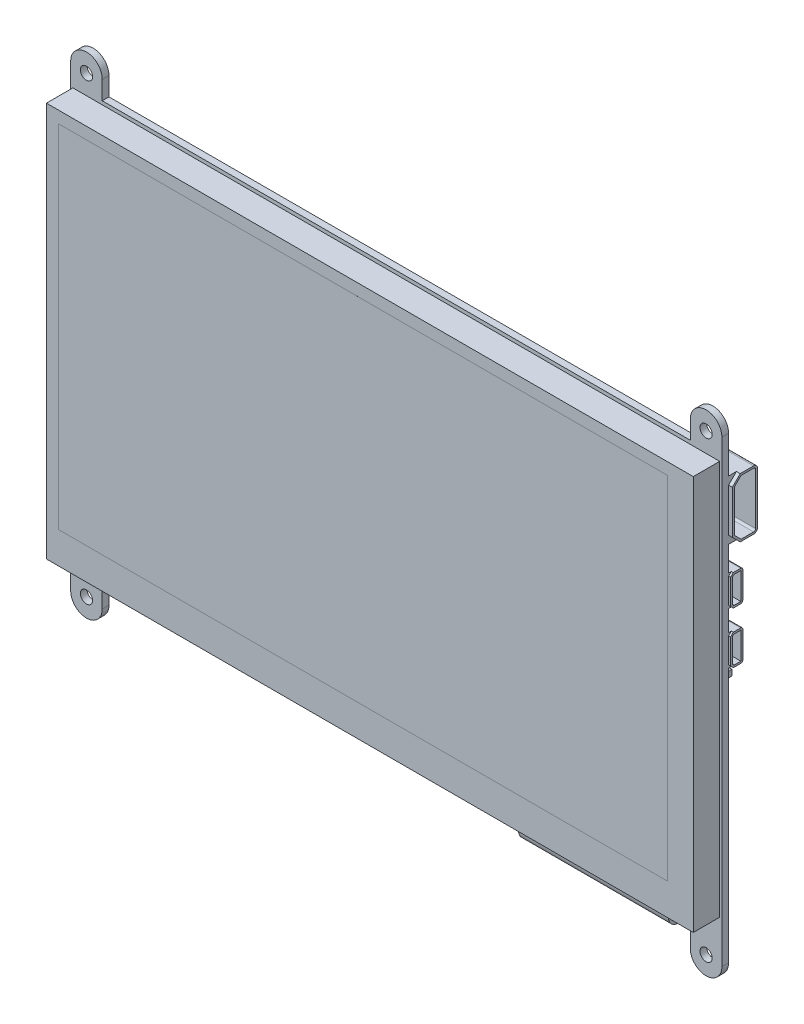
SolidWorks part; units mm, degrees
ref_plane "Přední rovina" through (0, 0, 0) normal (0, 0, 1) x (1, 0, 0)
ref_plane "Horní rovina" through (0, 0, 0) normal (0, 1, 0) x (1, 0, 0)
ref_plane "Pravá rovina" through (0, 0, 0) normal (1, 0, 0) x (0, 0, -1)
sketch "Skica1" plane through (0, 0, 0) normal (0, 0, 1) x (1, 0, 0)
  line L1 (-82, -50.05) -> (82, -50.05)
  line L2 (-82, -50.05) -> (-82, 50.05)
  line L3 (-82, 50.05) -> (82, 50.05)
  line L4 (82, -50.05) -> (82, 50.05)
  line L5 (-82, -50.05) -> (82, 50.05) construction
  line L6 (-82, 50.05) -> (82, -50.05) construction
  line L7 (-82.55, -55.95) -> (82.55, -55.95)
  line L8 (-82.55, -55.95) -> (-82.55, 50.95)
  line L9 (-82.55, 50.95) -> (82.55, 50.95)
  line L10 (82.55, -55.95) -> (82.55, 50.95)
  line L11 (-82.55, -55.95) -> (82.55, 50.95) construction
  line L12 (-82.55, 50.95) -> (82.55, -55.95) construction
  point P0 (0, 0)
  point P6 (0, -2.5)
  dimension "D1" = 100.1
  dimension "D2" = 164
  dimension "D3" = 106.9
  dimension "D4" = 0.55
  dimension "D5" = 0.55
  dimension "D6" = 0.9
extrude "Přidat vysunutím1" add sketch "Skica1" along normal blind 6.7 contours L1 L4 L3 L2 region at (0, 0, 0)
extrude "Přidat vysunutím2" add sketch "Skica1<3>" against normal blind 1.7 contours L10 L9 L8 L7
sketch "Skica1<3>" plane through (0, 0, 0) normal (0, 0, 1) x (1, 0, 0) same geometry as "Skica1"
sketch "Skica2" plane through (0, 0, -1.7) normal (0, 0, -1) x (-1, 0, 0)
  line L0 (0, 0) -> (0, -91.8363) construction
  line L1 (-82.55, -2.5) -> (0, -2.5) construction
  line L2 (-82.55, -55.95) -> (-82.55, 50.95) construction
  line L3 (-78.55, 50.95) -> (-78.55, 55.65) construction
  line L4 (82.55, 50.95) -> (-82.55, 50.95) construction
  line L5 (-82.55, 50.95) -> (-82.55, 55.65)
  line L6 (-74.55, 50.95) -> (-74.55, 55.65)
  line L7 (-78.55, -55.95) -> (-78.55, -60.65) construction
  line L8 (-82.55, -55.95) -> (-82.55, -60.65)
  line L9 (-74.55, -55.95) -> (-74.55, -60.65)
  line L10 (-78.55, -55.95) -> (-78.55, -60.65) construction
  line L11 (-82.55, -55.95) -> (-82.55, -60.65)
  line L12 (-74.55, -55.95) -> (-74.55, -60.65)
  line L13 (-78.55, 50.95) -> (-78.55, 55.65) construction
  line L14 (-82.55, 50.95) -> (-82.55, 55.65)
  line L15 (-74.55, 50.95) -> (-74.55, 55.65)
  line L16 (78.55, 50.95) -> (78.55, 55.65) construction
  line L17 (82.55, 50.95) -> (82.55, 55.65)
  line L18 (74.55, 50.95) -> (74.55, 55.65)
  line L19 (78.55, -55.95) -> (78.55, -60.65) construction
  line L20 (82.55, -55.95) -> (82.55, -60.65)
  line L21 (74.55, -55.95) -> (74.55, -60.65)
  line L22 (78.55, -55.95) -> (78.55, -60.65) construction
  line L23 (82.55, -55.95) -> (82.55, -60.65)
  line L24 (74.55, -55.95) -> (74.55, -60.65)
  line L25 (78.55, 50.95) -> (78.55, 55.65) construction
  line L26 (82.55, 50.95) -> (82.55, 55.65)
  line L27 (74.55, 50.95) -> (74.55, 55.65)
  arc A0 (-82.55, 50.95) -> (-74.55, 50.95) centre (-78.55, 50.95) ccw
  arc A1 (-74.55, 55.65) -> (-82.55, 55.65) centre (-78.55, 55.65) ccw
  circle A2 centre (-78.55, 55) radius 1.55
  circle A3 centre (-78.55, -60) radius 1.55
  arc A4 (-82.55, -55.95) -> (-74.55, -55.95) centre (-78.55, -55.95) cw
  arc A5 (-74.55, -60.65) -> (-82.55, -60.65) centre (-78.55, -60.65) cw
  arc A6 (-82.55, -55.95) -> (-74.55, -55.95) centre (-78.55, -55.95) cw
  arc A7 (-74.55, -60.65) -> (-82.55, -60.65) centre (-78.55, -60.65) cw
  arc A8 (-82.55, 50.95) -> (-74.55, 50.95) centre (-78.55, 50.95) ccw
  arc A9 (-74.55, 55.65) -> (-82.55, 55.65) centre (-78.55, 55.65) ccw
  circle A10 centre (-78.55, 55) radius 1.55
  circle A11 centre (-78.55, -60) radius 1.55
  circle A12 centre (78.55, -60) radius 1.55
  circle A13 centre (78.55, 55) radius 1.55
  circle A14 centre (78.55, -60) radius 1.55
  circle A15 centre (78.55, 55) radius 1.55
  arc A16 (82.55, 50.95) -> (74.55, 50.95) centre (78.55, 50.95) cw
  arc A17 (74.55, 55.65) -> (82.55, 55.65) centre (78.55, 55.65) cw
  arc A18 (82.55, -55.95) -> (74.55, -55.95) centre (78.55, -55.95) ccw
  arc A19 (74.55, -60.65) -> (82.55, -60.65) centre (78.55, -60.65) ccw
  arc A20 (82.55, -55.95) -> (74.55, -55.95) centre (78.55, -55.95) ccw
  arc A21 (74.55, -60.65) -> (82.55, -60.65) centre (78.55, -60.65) ccw
  arc A22 (82.55, 50.95) -> (74.55, 50.95) centre (78.55, 50.95) cw
  arc A23 (74.55, 55.65) -> (82.55, 55.65) centre (78.55, 55.65) cw
  point P11 (-78.55, 53.3)
  point P18 (-78.55, 59.65)
  point P23 (-78.55, -58.3)
  point P30 (-78.55, -58.3)
  point P37 (-78.55, 53.3)
  point P52 (78.55, 53.3)
  point P59 (78.55, -58.3)
  point P66 (78.55, -58.3)
  point P73 (78.55, 53.3)
  line M7 (-82.55, -55.95) -> (82.55, -55.95)
  line M9 (82.55, 50.95) -> (-82.55, 50.95)
  dimension "D1" = 8.7
  dimension "D2" = 3.1
  dimension "D4" = 3.1
  dimension "D3" = 8
extrude "Přidat vysunutím3" add sketch "Skica2" against normal up to surface (1.7 mm away) contours A5 L9 L8 A3 M7 | L21 A19 L20 A12 M7 | A17 L18 L17 A13 M9 | L6 A1 L5 A2 M9 region at (-74.6682, 53.3, -1.7) region at (82.4318, 53.3, -1.7) region at (78.55, -56.0682, -1.7) region at (-78.55, -56.0682, -1.7) up to face at (0, -2.5, 0)
sketch "Skica3" plane through (0, 0, 6.7) normal (0, 0, 1) x (1, 0, 0)
  line L0 (-82, 50.05) -> (82, 50.05) construction
  line L1 (75.5, 47.05) -> (-79, 47.05)
  line L2 (75.5, 47.05) -> (75.5, -42.05)
  line L3 (75.5, -42.05) -> (-79, -42.05)
  line L4 (-79, 47.05) -> (-79, -42.05)
  line L5 (75.5, 47.05) -> (-79, -42.05) construction
  line L6 (75.5, -42.05) -> (-79, 47.05) construction
  line L7 (-82, -50.05) -> (82, -50.05) construction
  line L8 (-82, -50.05) -> (-82, 50.05) construction
  line L9 (82, -50.05) -> (82, 50.05) construction
  point P0 (-1.75, 2.5)
  dimension "D1" = 3
  dimension "D2" = 8
  dimension "D3" = 3
  dimension "D4" = 6.5
extrude "Odebrat vysunutím1" cut sketch "Skica3" against normal blind 1.5
extrude "Přidat vysunutím4" add sketch "Skica3<2>" against normal blind 1.5 separate body
sketch "Skica3<2>" plane through (0, 0, 6.7) normal (0, 0, 1) x (1, 0, 0) same geometry as "Skica3"
sketch "Skica4" plane through (0, 0, 0) normal (0, 0, 1) x (1, 0, 0)
  line L0 (-82, -50.05) -> (82, -50.05) construction
  line L1 (75.3, -50.05) -> (37.3, -50.05)
  line L2 (75.3, -50.05) -> (75.3, -52.8)
  line L3 (75.3, -52.8) -> (37.3, -52.8)
  line L4 (37.3, -50.05) -> (37.3, -52.8)
  dimension "D1" = 38
  dimension "D2" = 2.75
  dimension "D3" = 6.7
extrude "Přidat vysunutím5" add sketch "Skica4" along normal blind 6.3
fillet "Zaoblit1" radius 2.5 1 edges at (56.3, -52.8, 6.3)
sketch "Skica5" plane through (0, 0, 0) normal (0, 0, 1) x (1, 0, 0)
  line L0 (-82, -50.05) -> (37.3, -50.05) construction
  line L1 (-14.55, -50.05) -> (13.95, -50.05)
  line L2 (-14.55, -50.05) -> (-14.55, -50.95)
  line L3 (-14.55, -50.95) -> (13.95, -50.95)
  line L4 (13.95, -50.05) -> (13.95, -50.95)
  line L5 (82.55, -60.65) -> (82.55, 55.65) construction
  dimension "D1" = 28.5
  dimension "D2" = 0.9
  dimension "D3" = 68.6
extrude "Přidat vysunutím6" add sketch "Skica5" along normal blind 4.3
fillet "Zaoblit2" radius 3 1 edges at (-0.3, -50.95, 4.3)
sketch "Skica6" plane through (0, 0, -1.7) normal (0, 0, -1) x (-1, 0, 0)
  line L0 (74.55, 50.95) -> (-74.55, 50.95) construction
  line L1 (-21.65, 11.45) -> (-1.75, 11.45)
  line L2 (-21.65, 11.45) -> (-21.65, 25.25)
  line L3 (-21.65, 25.25) -> (-1.75, 25.25)
  line L4 (-1.75, 11.45) -> (-1.75, 25.25)
  line L5 (-21.65, 11.45) -> (-1.75, 25.25) construction
  line L6 (-21.65, 25.25) -> (-1.75, 11.45) construction
  line L7 (-23.55, 11.95) -> (0.15, 11.95)
  line L8 (-23.55, 11.95) -> (-23.55, 24.75)
  line L9 (-23.55, 24.75) -> (0.15, 24.75)
  line L10 (0.15, 11.95) -> (0.15, 24.75)
  line L11 (-23.55, 11.95) -> (0.15, 24.75) construction
  line L12 (-23.55, 24.75) -> (0.15, 11.95) construction
  line L13 (-21.1, 9.45) -> (-2.3, 9.45)
  line L14 (-21.1, 9.45) -> (-21.1, 27.25)
  line L15 (-21.1, 27.25) -> (-2.3, 27.25)
  line L16 (-2.3, 9.45) -> (-2.3, 27.25)
  line L17 (-21.1, 9.45) -> (-2.3, 27.25) construction
  line L18 (-21.1, 27.25) -> (-2.3, 9.45) construction
  line L19 (-82.55, -60.65) -> (-82.55, 55.65) construction
  line L20 (82.55, -60.65) -> (82.55, 55.65) construction
  line L21 (32.45, 6.95) -> (66.45, 6.95)
  line L22 (32.45, 6.95) -> (32.45, 29.35)
  line L23 (32.45, 29.35) -> (66.45, 29.35)
  line L24 (66.45, 6.95) -> (66.45, 29.35)
  line L25 (26.55, 23.25) -> (18.25, 23.25)
  line L26 (26.55, 23.25) -> (26.55, 6.85)
  line L27 (26.55, 6.85) -> (18.25, 6.85)
  line L28 (18.25, 23.25) -> (18.25, 6.85)
  line L29 (18.25, 23.25) -> (13.85, 23.25)
  line L30 (18.25, 23.25) -> (18.25, 12.25)
  line L31 (18.25, 12.25) -> (13.85, 12.25)
  line L32 (13.85, 23.25) -> (13.85, 12.25)
  line L33 (2.75, 12.85) -> (5.65, 12.85)
  line L34 (2.75, 12.85) -> (2.75, 30.05)
  line L35 (2.75, 30.05) -> (5.65, 30.05)
  line L36 (5.65, 12.85) -> (5.65, 30.05)
  line L37 (5.65, 30.05) -> (9.75, 30.05)
  line L38 (5.65, 30.05) -> (5.65, 25.75)
  line L39 (5.65, 25.75) -> (9.75, 25.75)
  line L40 (9.75, 30.05) -> (9.75, 25.75)
  point P0 (-11.7, 18.35)
  point P5 (-11.7, 18.35)
  point P10 (-11.7, 18.35)
  point P40 (9.75, 27.9)
  dimension "D1" = 19.9
  dimension "D2" = 13.8
  dimension "D3" = 12.8
  dimension "D4" = 18.8
  dimension "D5" = 23.7
  dimension "D6" = 17.8
  dimension "D7" = 25.7
  dimension "D8" = 60.9
  dimension "D9" = 34
  dimension "D10" = 22.4
  dimension "D11" = 16.1
  dimension "D12" = 21.6
  dimension "D13" = 8.3
  dimension "D14" = 12.7
  dimension "D15" = 16.4
  dimension "D16" = 11
  dimension "D17" = 27.7
  dimension "D18" = 56
  dimension "D19" = 17.2
  dimension "D20" = 7
  dimension "D21" = 4.3
  dimension "D22" = 20.9
  dimension "D23" = 72.8
  dimension "D24" = 2.9
extrude "Přidat vysunutím7" add sketch "Skica6" along normal blind 2.4 contours L21 L24 L23 L22 region at (-49.45, 18.15, -1.7)
extrude "Přidat vysunutím8" add sketch "Skica6<3>" along normal blind 1.8 contours L25 L28 L27 L26 region at (-22.4, 15.05, -1.7)
sketch "Skica6<3>" plane through (0, 0, -1.7) normal (0, 0, -1) x (-1, 0, 0) same geometry as "Skica6"
extrude "Přidat vysunutím9" add sketch "Skica6<4>" along normal blind 1 contours L29 L32 L31 L28 region at (-16.05, 17.75, -1.7)
sketch "Skica6<4>" plane through (0, 0, -1.7) normal (0, 0, -1) x (-1, 0, 0) same geometry as "Skica6"
extrude "Přidat vysunutím10" add sketch "Skica6<5>" along normal blind 1 contours L33 L36 L35 L34 | L37 L40 L39 L38 region at (-4.2, 21.45, -1.7)
sketch "Skica6<5>" plane through (0, 0, -1.7) normal (0, 0, -1) x (-1, 0, 0) same geometry as "Skica6"
extrude "Přidat vysunutím11" add sketch "Skica6<6>" along normal blind 1.45 contours L2 L3 L4 L1
sketch "Skica6<6>" plane through (0, 0, -1.7) normal (0, 0, -1) x (-1, 0, 0) same geometry as "Skica6"
extrude "Přidat vysunutím12" add sketch "Skica6<7>" along normal blind 0.8 contours L7 L10 L9 L4 | L15 L16 L13 L14 | L8 L9 L10 L7 region at (0.8, 18.35, -1.7)
sketch "Skica6<7>" plane through (0, 0, -1.7) normal (0, 0, -1) x (-1, 0, 0) same geometry as "Skica6"
chamfer "Zkosení1" distance 0.8 angle 45 4 edges at (11.7, 27.25, -2.5) (23.55, 18.35, -2.5) (-0.15, 18.35, -2.5) (11.7, 9.45, -2.5)
sketch "Skica7" plane through (0, 0, -1.7) normal (0, 0, -1) x (-1, 0, 0)
  line L0 (74.55, -55.95) -> (-74.55, -55.95) construction
  line L1 (-35.45, -32.65) -> (-28.65, -32.65)
  line L2 (-35.45, -32.65) -> (-35.45, -25.85)
  line L3 (-35.45, -25.85) -> (-28.65, -25.85)
  line L4 (-28.65, -32.65) -> (-28.65, -25.85)
  line L5 (-35.45, -32.65) -> (-28.65, -25.85) construction
  line L6 (-35.45, -25.85) -> (-28.65, -32.65) construction
  line L7 (-34.9, -34.25) -> (-29.2, -34.25)
  line L8 (-34.9, -34.25) -> (-34.9, -24.25)
  line L9 (-34.9, -24.25) -> (-29.2, -24.25)
  line L10 (-29.2, -34.25) -> (-29.2, -24.25)
  line L11 (-34.9, -34.25) -> (-29.2, -24.25) construction
  line L12 (-34.9, -24.25) -> (-29.2, -34.25) construction
  line L13 (-37.05, -32.1) -> (-27.05, -32.1)
  line L14 (-37.05, -32.1) -> (-37.05, -26.4)
  line L15 (-37.05, -26.4) -> (-27.05, -26.4)
  line L16 (-27.05, -32.1) -> (-27.05, -26.4)
  line L17 (-37.05, -32.1) -> (-27.05, -26.4) construction
  line L18 (-37.05, -26.4) -> (-27.05, -32.1) construction
  line L19 (-82.55, -60.65) -> (-82.55, 55.65) construction
  line L20 (-45.9, -24.6) -> (-45.9, -31) construction
  line L21 (-24.15, -32.45) -> (-21.85, -32.45)
  line L22 (-24.15, -32.45) -> (-24.15, -24.65)
  line L23 (-24.15, -24.65) -> (-21.85, -24.65)
  line L24 (-21.85, -32.45) -> (-21.85, -24.65)
  line L25 (-34.05, -21.85) -> (-29.55, -21.85)
  line L26 (-34.05, -21.85) -> (-34.05, -19.35)
  line L27 (-34.05, -19.35) -> (-29.55, -19.35)
  line L28 (-29.55, -21.85) -> (-29.55, -19.35)
  line L29 (-42.15, -35.15) -> (-40.5, -35.15)
  line L30 (-42.15, -35.15) -> (-42.15, -24.85)
  line L31 (-42.15, -24.85) -> (-40.5, -24.85)
  line L32 (-40.5, -35.15) -> (-40.5, -24.85)
  line L33 (-40.5, -35.15) -> (-38.85, -35.15)
  line L34 (-40.5, -35.15) -> (-40.5, -29.25)
  line L35 (-40.5, -29.25) -> (-38.85, -29.25)
  line L36 (-38.85, -35.15) -> (-38.85, -29.25)
  line L37 (-44.15, -24.6) -> (-44.15, -31)
  line L38 (-47.65, -24.6) -> (-47.65, -31)
  line L39 (-45.9, -31) -> (-45.9, -24.6) construction
  line L40 (-48.15, -31) -> (-48.15, -24.6)
  line L41 (-43.65, -31) -> (-43.65, -24.6)
  line L43 (-29.55, -37.45) -> (-27.55, -37.45)
  line L44 (-29.55, -37.45) -> (-29.55, -36.15)
  line L45 (-29.55, -36.15) -> (-27.55, -36.15)
  line L46 (-27.55, -37.45) -> (-27.55, -36.15)
  arc A0 (-44.15, -24.6) -> (-47.65, -24.6) centre (-45.9, -24.6) ccw
  arc A1 (-47.65, -31) -> (-44.15, -31) centre (-45.9, -31) ccw
  arc A2 (-48.15, -31) -> (-43.65, -31) centre (-45.9, -31) ccw
  arc A3 (-43.65, -24.6) -> (-48.15, -24.6) centre (-45.9, -24.6) ccw
  point P0 (-32.05, -29.25)
  point P5 (-32.05, -29.25)
  point P10 (-32.05, -29.25)
  point P36 (-45.9, -27.8)
  point P41 (-45.9, -27.8)
  point P48 (-45.9, -32.75)
  point P49 (-47.65, -27.8)
  dimension "D10" = 23.2
  dimension "D1" = 6.8
  dimension "D2" = 5.7
  dimension "D3" = 10
  dimension "D4" = 23.3
  dimension "D5" = 47.1
  dimension "D6" = 4.5
  dimension "D7" = 3.5
  dimension "D8" = 9.9
  dimension "D9" = 34.9
  dimension "D11" = 3.3
  dimension "D12" = 10.3
  dimension "D13" = 5.9
  dimension "D14" = 20.8
  dimension "D15" = 40.4
  dimension "D16" = 2.3
  dimension "D17" = 7.8
  dimension "D18" = 23.5
  dimension "D19" = 4.5
  dimension "D20" = 4.5
  dimension "D21" = 2.5
  dimension "D22" = 4
  dimension "D23" = 48.5
  dimension "D24" = 2
  dimension "D25" = 1.3
  dimension "D26" = 18.5
  dimension "D27" = 53
extrude "Přidat vysunutím13" add sketch "Skica7" along normal blind 1.5 contours L1 L4 L3 L2
extrude "Přidat vysunutím14" add sketch "Skica7<3>" along normal blind 0.8 contours L16 L15 L14 L13 | L9 L10 L7 L8
sketch "Skica7<3>" plane through (0, 0, -1.7) normal (0, 0, -1) x (-1, 0, 0) same geometry as "Skica7"
extrude "Přidat vysunutím15" add sketch "Skica7<4>" along normal blind 0.7 contours L41 A3 L40 A2
sketch "Skica7<4>" plane through (0, 0, -1.7) normal (0, 0, -1) x (-1, 0, 0) same geometry as "Skica7"
extrude "Přidat vysunutím16" add sketch "Skica7<5>" along normal blind 4.2 contours L37 A1 L38 A0
sketch "Skica7<5>" plane through (0, 0, -1.7) normal (0, 0, -1) x (-1, 0, 0) same geometry as "Skica7"
extrude "Přidat vysunutím17" add sketch "Skica7<6>" along normal blind 0.8 contours L33 L36 L35 L34 | L29 L30 L31 L32 | L24 L23 L22 L21 | L43 L46 L45 L44 | L25 L28 L27 L26
sketch "Skica7<6>" plane through (0, 0, -1.7) normal (0, 0, -1) x (-1, 0, 0) same geometry as "Skica7"
chamfer "Zkosení2" distance 0.8 angle 45 4 edges at (32.05, -24.25, -2.5) (37.05, -29.25, -2.5) (27.05, -29.25, -2.5) (32.05, -34.25, -2.5)
sketch "Skica8" plane through (0, 0, -1.7) normal (0, 0, -1) x (-1, 0, 0)
  line L0 (74.55, -55.95) -> (-74.55, -55.95) construction
  line L1 (-17.15, -36.45) -> (20.55, -36.45)
  line L2 (-17.15, -36.45) -> (-17.15, -31.45)
  line L3 (-17.15, -31.45) -> (20.55, -31.45)
  line L4 (20.55, -36.45) -> (20.55, -31.45)
  line L5 (82.55, -60.65) -> (82.55, 55.65) construction
  dimension "D1" = 5
  dimension "D2" = 37.7
  dimension "D3" = 19.5
  dimension "D4" = 62
extrude "Odebrat vysunutím2" cut sketch "Skica8" against normal blind 1.6
sketch "Skica9" plane through (0, 0, -1.7) normal (0, 0, -1) x (-1, 0, 0)
  line L0 (1.1, -10.85) -> (1.1, -1.0919) construction
  line L1 (13.9, -12.85) -> (-11.7, -12.85)
  line L2 (13.9, -12.85) -> (13.9, -8.85)
  line L3 (13.9, -8.85) -> (-11.7, -8.85)
  line L4 (-11.7, -12.85) -> (-11.7, -8.85)
  line L5 (13.9, -12.85) -> (-11.7, -8.85) construction
  line L6 (13.9, -8.85) -> (-11.7, -12.85) construction
  line L7 (-14.05, -13.35) -> (-11.7, -13.35)
  line L8 (-14.05, -13.35) -> (-14.05, -8.35)
  line L9 (-14.05, -8.35) -> (-11.7, -8.35)
  line L10 (-11.7, -13.35) -> (-11.7, -8.35)
  line L11 (-14.05, -13.35) -> (-11.7, -8.35) construction
  line L12 (-14.05, -8.35) -> (-11.7, -13.35) construction
  line L13 (16.25, -8.35) -> (13.9, -13.35) construction
  line L14 (13.9, -12.85) -> (13.9, -8.85)
  line L15 (16.25, -13.35) -> (13.9, -8.35) construction
  line L16 (13.9, -13.35) -> (13.9, -8.35)
  line L17 (16.25, -13.35) -> (13.9, -13.35)
  line L18 (16.25, -8.35) -> (13.9, -8.35)
  line L19 (16.25, -13.35) -> (16.25, -8.35)
  line L20 (82.55, -60.65) -> (82.55, 55.65) construction
  line L21 (74.55, -55.95) -> (-74.55, -55.95) construction
  point P0 (1.1, -10.85)
  point P5 (-12.875, -10.85)
  point P10 (15.075, -10.85)
  dimension "D1" = 4
  dimension "D2" = 30.3
  dimension "D3" = 25.6
  dimension "D4" = 5
  dimension "D5" = 66.3
  dimension "D6" = 43.1
extrude "Přidat vysunutím18" add sketch "Skica9" along normal blind 2 contours L4 L1 L2 L3 region at (-1.1, -10.85, -1.7)
extrude "Přidat vysunutím19" add sketch "Skica9<3>" along normal blind 2.1 contours L8 L9 L10 L7 | L19 L18 L16 L17
sketch "Skica9<3>" plane through (0, 0, -1.7) normal (0, 0, -1) x (-1, 0, 0) same geometry as "Skica9"
chamfer "Zkosení3" distance 0.5 angle 45 1 edges at (-1.1, -8.85, -1.7)
sketch "Skica10" plane through (0, 0, -1.7) normal (0, 0, -1) x (-1, 0, 0)
  line L0 (13.9, -12.85) -> (-11.7, -12.85) construction
  line L1 (-11.7, -12.85) -> (13.9, -12.85)
  line L2 (-11.7, -12.85) -> (-11.7, -33.85)
  line L3 (-11.7, -33.85) -> (13.9, -33.85)
  line L4 (13.9, -12.85) -> (13.9, -33.85)
  line L5 (-14.6, -29.35) -> (-11.7, -24.85)
  line L6 (-11.7, -33.85) -> (-14.6, -33.85)
  line L7 (-11.7, -33.85) -> (-11.7, -29.35)
  line L8 (-11.7, -29.35) -> (-14.6, -29.35)
  line L9 (-14.6, -33.85) -> (-14.6, -29.35)
  dimension "D1" = 21
  dimension "D2" = 28.5
  dimension "D3" = 16.5
  dimension "D4" = 4.5
extrude "Přidat vysunutím20" add sketch "Skica10" along direction (0, 0, 1) on the side against the normal up to surface (1.6 mm away) and the other way blind 1.25 contours L4 L1 L2 L3 | L9 L6 L2 L8 | L8 L2 L5 region at (-1.1, -23.35, -1.7) region at (12.6667, -27.85, -1.7) region at (13.15, -31.6, -1.7) up to face at (-1.7, -33.95, -0.1)
fillet "Zaoblit3" radius 3 1 edges at (0.35, -33.85, -2.95)
sketch "Skica11" plane through (0, 0, -1.7) normal (0, 0, -1) x (-1, 0, 0)
  line L0 (-36.95, -7.85) -> (-36.95, 5.6861) construction
  line L5 (74.55, -55.95) -> (-74.55, -55.95) construction
  line L6 (-82.55, -60.65) -> (-82.55, 55.65) construction
  line L7 (-40.15, -9.55) -> (-33.75, -9.55)
  line L8 (-40.15, -9.55) -> (-40.15, -6.15)
  line L9 (-40.15, -6.15) -> (-33.75, -6.15)
  line L10 (-33.75, -9.55) -> (-33.75, -6.15)
  line L11 (-40.15, -9.55) -> (-33.75, -6.15) construction
  line L12 (-40.15, -6.15) -> (-33.75, -9.55) construction
  line L13 (-38.45, -3.65) -> (-35.45, -3.65)
  line L14 (-38.45, -3.65) -> (-38.45, -6.15)
  line L15 (-38.45, -6.15) -> (-35.45, -6.15)
  line L16 (-35.45, -3.65) -> (-35.45, -6.15)
  line L17 (-38.45, -3.65) -> (-35.45, -6.15) construction
  line L18 (-38.45, -6.15) -> (-35.45, -3.65) construction
  line L19 (-36.575, -11.65) -> (-37.325, -11.65)
  line L20 (-36.575, -11.65) -> (-36.575, -9.55)
  line L21 (-36.575, -9.55) -> (-37.325, -9.55)
  line L22 (-37.325, -11.65) -> (-37.325, -9.55)
  line L23 (-36.575, -11.65) -> (-37.325, -9.55) construction
  line L24 (-36.575, -9.55) -> (-37.325, -11.65) construction
  line L25 (-39.575, -11.65) -> (-38.825, -11.65)
  line L26 (-39.575, -11.65) -> (-39.575, -9.55)
  line L27 (-39.575, -9.55) -> (-38.825, -9.55)
  line L28 (-38.825, -11.65) -> (-38.825, -9.55)
  line L29 (-39.575, -11.65) -> (-38.825, -9.55) construction
  line L30 (-39.575, -9.55) -> (-38.825, -11.65) construction
  line L31 (-34.325, -9.55) -> (-35.075, -11.65) construction
  line L32 (-34.325, -11.65) -> (-35.075, -9.55) construction
  line L33 (-35.075, -11.65) -> (-35.075, -9.55)
  line L34 (-34.325, -11.65) -> (-34.325, -9.55)
  line L35 (-34.325, -11.65) -> (-35.075, -11.65)
  line L36 (-40.15, 2.45) -> (-33.75, 2.45)
  line L37 (-40.15, 2.45) -> (-40.15, 5.85)
  line L38 (-40.15, 5.85) -> (-33.75, 5.85)
  line L39 (-33.75, 2.45) -> (-33.75, 5.85)
  line L40 (-38.45, 8.35) -> (-35.45, 8.35)
  line L41 (-38.45, 8.35) -> (-38.45, 5.85)
  line L42 (-38.45, 5.85) -> (-35.45, 5.85)
  line L43 (-35.45, 8.35) -> (-35.45, 5.85)
  line L44 (-36.575, 0.35) -> (-37.325, 0.35)
  line L45 (-36.575, 0.35) -> (-36.575, 2.45)
  line L46 (-36.575, 2.45) -> (-37.325, 2.45)
  line L47 (-37.325, 0.35) -> (-37.325, 2.45)
  line L48 (-39.575, 0.35) -> (-38.825, 0.35)
  line L49 (-39.575, 0.35) -> (-39.575, 2.45)
  line L50 (-39.575, 2.45) -> (-38.825, 2.45)
  line L51 (-38.825, 0.35) -> (-38.825, 2.45)
  line L52 (-35.075, 0.35) -> (-35.075, 2.45)
  line L53 (-34.325, 0.35) -> (-34.325, 2.45)
  line L54 (-34.325, 0.35) -> (-35.075, 0.35)
  line L55 (-36.95, 4.15) -> (-36.95, 17.6861) construction
  line L56 (-40.15, 2.45) -> (-33.75, 5.85) construction
  line L57 (-40.15, 5.85) -> (-33.75, 2.45) construction
  line L58 (-38.45, 8.35) -> (-35.45, 5.85) construction
  line L59 (-38.45, 5.85) -> (-35.45, 8.35) construction
  line L60 (-36.575, 0.35) -> (-37.325, 2.45) construction
  line L61 (-36.575, 2.45) -> (-37.325, 0.35) construction
  line L62 (-39.575, 0.35) -> (-38.825, 2.45) construction
  line L63 (-39.575, 2.45) -> (-38.825, 0.35) construction
  line L64 (-34.325, 2.45) -> (-35.075, 0.35) construction
  line L65 (-34.325, 0.35) -> (-35.075, 2.45) construction
  point P5 (-36.95, -7.85)
  point P10 (-36.95, -4.9)
  point P15 (-36.95, -10.6)
  point P20 (-39.2, -10.6)
  point P32 (-34.7, -10.6)
  point P34 (-36.95, 4.15)
  point P39 (-36.95, 7.1)
  point P44 (-36.95, 1.4)
  point P49 (-39.2, 1.4)
  point P58 (-34.7, 1.4)
  dimension "D1" = 6.4
  dimension "D2" = 3.4
  dimension "D3" = 0.75
  dimension "D4" = 3
  dimension "D5" = 3
  dimension "D6" = 2.1
  dimension "D7" = 2.5
  dimension "D8" = 49.8
  dimension "D9" = 48.8
  dimension "D10" = 2
extrude "Přidat vysunutím21" add sketch "Skica11" along normal blind 1.9 contours L7 L10 L9 L8 | L36 L39 L38 L37 region at (36.95, -7.85, -1.7) region at (36.95, 4.15, -1.7)
extrude "Přidat vysunutím23" add sketch "Skica11<3>" along normal blind 0.8 contours L35 L34 L7 L33 | L43 L40 L41 L38 | L48 L51 L36 L49 | L47 L44 L45 L36 | L54 L53 L36 L52 | L14 L15 L16 L13 | L26 L27 L28 L25 | L22 L21 L20 L19 region at (34.7, -10.6, -1.7) region at (39.2, 1.4, -1.7) region at (36.95, 7.1, -1.7) region at (36.95, 1.4, -1.7) region at (34.7, 1.4, -1.7)
sketch "Skica11<3>" plane through (0, 0, -1.7) normal (0, 0, -1) x (-1, 0, 0) same geometry as "Skica11"
chamfer "Zkosení4" distance 0.8 angle 45 8 edges at (39.2, 0.35, -2.5) (34.7, 0.35, -2.5) (36.95, 0.35, -2.5) (36.95, 8.35, -2.5) (36.95, -3.65, -2.5) (34.7, -11.65, -2.5) (36.95, -11.65, -2.5) (39.2, -11.65, -2.5)
sketch "Skica12" plane through (0, 0, -1.7) normal (0, 0, -1) x (-1, 0, 0)
  line L0 (74.55, 50.95) -> (-74.55, 50.95) construction
  line L1 (-30.35, -11.65) -> (-27.85, -11.65)
  line L2 (-30.35, -11.65) -> (-30.35, -4.15)
  line L3 (-30.35, -4.15) -> (-27.85, -4.15)
  line L4 (-27.85, -11.65) -> (-27.85, -4.15)
  line L5 (-30.35, 1.75) -> (-27.85, 1.75)
  line L6 (-30.35, 1.75) -> (-30.35, 4.95)
  line L7 (-30.35, 4.95) -> (-27.85, 4.95)
  line L8 (-27.85, 1.75) -> (-27.85, 4.95)
  line L9 (-30.35, 10.15) -> (-27.85, 10.15)
  line L10 (-30.35, 10.15) -> (-30.35, 14.65)
  line L11 (-30.35, 14.65) -> (-27.85, 14.65)
  line L12 (-27.85, 10.15) -> (-27.85, 14.65)
  line L13 (-30.35, 18.65) -> (-27.85, 18.65)
  line L14 (-30.35, 18.65) -> (-30.35, 19.65)
  line L15 (-30.35, 19.65) -> (-27.85, 19.65)
  line L16 (-27.85, 18.65) -> (-27.85, 19.65)
  line L17 (-16.55, -2.75) -> (-5.55, -2.75)
  line L18 (-16.55, -2.75) -> (-16.55, -0.25)
  line L19 (-16.55, -0.25) -> (-5.55, -0.25)
  line L20 (-5.55, -2.75) -> (-5.55, -0.25)
  line L21 (-14.25, 30.25) -> (-11.45, 30.25)
  line L22 (-14.25, 30.25) -> (-14.25, 32.75)
  line L23 (-14.25, 32.75) -> (-11.45, 32.75)
  line L24 (-11.45, 30.25) -> (-11.45, 32.75)
  line L25 (-1.95, 30.25) -> (0.85, 30.25)
  line L26 (-1.95, 30.25) -> (-1.95, 32.75)
  line L27 (-1.95, 32.75) -> (0.85, 32.75)
  line L28 (0.85, 30.25) -> (0.85, 32.75)
  line L29 (-18.65, 4.05) -> (-17.65, 4.05)
  line L30 (-18.65, 4.05) -> (-18.65, 6.55)
  line L31 (-18.65, 6.55) -> (-17.65, 6.55)
  line L32 (-17.65, 4.05) -> (-17.65, 6.55)
  line L33 (-12.15, 4.05) -> (-11.15, 4.05)
  line L34 (-12.15, 4.05) -> (-12.15, 6.55)
  line L35 (-12.15, 6.55) -> (-11.15, 6.55)
  line L36 (-11.15, 4.05) -> (-11.15, 6.55)
  line L37 (-82.55, -60.65) -> (-82.55, 55.65) construction
  dimension "D1" = 11
  dimension "D2" = 2.5
  dimension "D3" = 7.5
  dimension "D4" = 3.2
  dimension "D5" = 4.5
  dimension "D6" = 1
  dimension "D7" = 31.3
  dimension "D8" = 31.3
  dimension "D9" = 5.9
  dimension "D10" = 5.2
  dimension "D11" = 52.2
  dimension "D12" = 18.2
  dimension "D13" = 2.8
  dimension "D14" = 9.5
  dimension "D15" = 68.3
  dimension "D16" = 5.5
  dimension "D17" = 46.9
  dimension "D18" = 63.9
  dimension "D19" = 66
  dimension "D20" = 51.2
extrude "Přidat vysunutím24" add sketch "Skica12" along normal blind 1.6
sketch "Skica14" plane through (0, 0, -1.7) normal (0, 0, -1) x (-1, 0, 0)
  line L0 (-5.55, -2.75) -> (-5.55, -0.25) construction
  line L1 (8.55, -2.75) -> (10.95, -2.75)
  line L2 (8.55, -2.75) -> (8.55, -0.05)
  line L3 (8.55, -0.05) -> (10.95, -0.05)
  line L4 (10.95, -2.75) -> (10.95, -0.05)
  line L5 (10.95, -2.75) -> (12.35, -2.75)
  line L6 (10.95, -2.75) -> (10.95, 1.25)
  line L7 (10.95, 1.25) -> (12.35, 1.25)
  line L8 (12.35, -2.75) -> (12.35, 1.25)
  line L9 (12.35, -2.75) -> (16.75, -2.75)
  line L10 (12.35, -2.75) -> (12.35, -0.05)
  line L11 (12.35, -0.05) -> (16.75, -0.05)
  line L12 (16.75, -2.75) -> (16.75, -0.05)
  line L13 (-16.55, -2.75) -> (-5.55, -2.75) construction
  dimension "D1" = 8.2
  dimension "D2" = 2.7
  dimension "D3" = 4
  dimension "D4" = 4.4
  dimension "D5" = 1.4
  dimension "D6" = 14.1
extrude "Přidat vysunutím25" add sketch "Skica14" along normal blind 0.8 contours L1 L4 L3 L2 | L9 L12 L11 L8 region at (-9.75, -1.4, -1.7) region at (-14.55, -1.4, -1.7)
extrude "Přidat vysunutím26" add sketch "Skica14<3>" along normal blind 1.6 contours L5 L8 L7 L6 L4 region at (-11.65, -0.75, -1.7)
sketch "Skica14<3>" plane through (0, 0, -1.7) normal (0, 0, -1) x (-1, 0, 0) same geometry as "Skica14"
sketch "Skica15" plane through (0, 0, -1.7) normal (0, 0, -1) x (-1, 0, 0)
  line L0 (74.55, 50.95) -> (-74.55, 50.95) construction
  line L1 (-67.25, 42.15) -> (-59.35, 42.15)
  line L2 (-67.25, 42.15) -> (-67.25, 44.95)
  line L3 (-67.25, 44.95) -> (-59.35, 44.95)
  line L4 (-59.35, 42.15) -> (-59.35, 44.95)
  line L5 (-66.75, 37.35) -> (-60.35, 37.35)
  line L6 (-66.75, 37.35) -> (-66.75, 40.15)
  line L7 (-66.75, 40.15) -> (-60.35, 40.15)
  line L8 (-60.35, 37.35) -> (-60.35, 40.15)
  line L9 (-82.55, -60.65) -> (-82.55, 55.65) construction
  dimension "D1" = 2.8
  dimension "D2" = 7.9
  dimension "D3" = 6.4
  dimension "D4" = 2
  dimension "D5" = 1
  dimension "D6" = 6
  dimension "D7" = 15.8
extrude "Přidat vysunutím27" add sketch "Skica15" along normal blind 1.2
sketch "Skica17" plane through (0, 0, -1.7) normal (0, 0, -1) x (-1, 0, 0)
  line L0 (74.55, -55.95) -> (-74.55, -55.95) construction
  line L1 (-60.05, 7.55) -> (-54.85, 7.55)
  line L2 (-60.05, 7.55) -> (-60.05, 9.45)
  line L3 (-60.05, 9.45) -> (-54.85, 9.45)
  line L4 (-54.85, 7.55) -> (-54.85, 9.45)
  line L5 (-82.55, -60.65) -> (-82.55, 55.65) construction
  dimension "D1" = 5.2
  dimension "D2" = 1.9
  dimension "D3" = 63.5
  dimension "D4" = 22.5
extrude "Odebrat vysunutím3" cut sketch "Skica17" against normal blind 1.6
sketch "Skica18" plane through (0, 0, -1.7) normal (0, 0, -1) x (-1, 0, 0)
  line L0 (-60.05, 7.55) -> (-54.85, 7.55) construction
  line L1 (-54.05, 21.35) -> (-61.45, 21.35)
  line L2 (-54.05, 21.35) -> (-54.05, 26.85)
  line L3 (-54.05, 26.85) -> (-61.45, 26.85)
  line L4 (-61.45, 21.35) -> (-61.45, 26.85)
  line L5 (-54.05, 21.35) -> (-61.45, 26.85) construction
  line L6 (-54.05, 26.85) -> (-61.45, 21.35) construction
  line L7 (-59.5, 21.35) -> (-56, 21.35)
  line L8 (-59.5, 21.35) -> (-59.5, 8.05)
  line L9 (-59.5, 8.05) -> (-56, 8.05)
  line L10 (-56, 21.35) -> (-56, 8.05)
  line L11 (74.55, 50.95) -> (-74.55, 50.95) construction
  line L12 (-82.55, -60.65) -> (-82.55, 55.65) construction
  line L13 (-57.75, 24.1) -> (-57.75, 18.4003) construction
  point P0 (-57.75, 24.1)
  dimension "D1" = 0.5
  dimension "D2" = 24.1
  dimension "D3" = 7.4
  dimension "D4" = 21.1
  dimension "D5" = 5.5
  dimension "D6" = 3.5
extrude "Přidat vysunutím28" add sketch "Skica18" along normal blind 2.4 contours L2 L3 L4 L1
extrude "Přidat vysunutím29" add sketch "Skica18<3>" along normal blind 0.5 and the other way up to surface (1.6 mm away) contours L10 L1 L8 L9 region at (57.75, 14.7, -1.7) other way up to face at (57.45, 8.5, -0.1)
sketch "Skica18<3>" plane through (0, 0, -1.7) normal (0, 0, -1) x (-1, 0, 0) same geometry as "Skica18"
fillet "Zaoblit4" radius 2 1 edges at (57.75, 8.05, -2.2)
sketch "Skica19" plane through (0, 0, -1.7) normal (0, 0, -1) x (-1, 0, 0)
  line L0 (-82, -50.05) -> (-82, 50.05) construction
  line L1 (-71.8, 31.25) -> (-83.5, 31.25)
  line L2 (-71.8, 31.25) -> (-71.8, 46.25)
  line L3 (-71.8, 46.25) -> (-83.5, 46.25)
  line L4 (-83.5, 31.25) -> (-83.5, 46.25)
  line L5 (74.55, 50.95) -> (-74.55, 50.95) construction
  dimension "D1" = 15
  dimension "D2" = 11.7
  dimension "D3" = 1.5
  dimension "D4" = 4.7
extrude "Přidat vysunutím30" add sketch "Skica19" along normal blind 6.4
fillet "Zaoblit5" radius 1 2 edges at (77.65, 46.25, -8.1) (77.65, 31.25, -8.1)
chamfer "Zkosení5" distance 2 angle 45 2 edges at (83.025, 31.25, -1.7) (83.025, 46.25, -1.7)
sketch "Skica20" plane through (83.5, 0, 0) normal (1, 0, 0) x (0, 0, -1)
  line L0 (2.2, 44.0429) -> (2.2, 33.4571)
  line L1 (2.2, 33.4571) -> (3.9071, 31.75)
  line L2 (3.9071, 31.75) -> (7.1, 31.75)
  line L3 (7.6, 32.25) -> (7.6, 45.25)
  line L4 (7.1, 45.75) -> (3.9071, 45.75)
  line L5 (3.9071, 45.75) -> (2.2, 44.0429)
  line L6 (1.7, 44.25) -> (1.7, 33.25)
  line L7 (1.7, 33.25) -> (3.7, 31.25)
  line L8 (3.7, 31.25) -> (7.1, 31.25)
  line L9 (8.1, 32.25) -> (8.1, 45.25)
  line L10 (7.1, 46.25) -> (3.7, 46.25)
  line L11 (3.7, 46.25) -> (1.7, 44.25)
  line L12 (1.7, 44.25) -> (1.7, 33.25)
  line L13 (1.7, 33.25) -> (3.7, 31.25)
  line L14 (3.7, 31.25) -> (7.1, 31.25)
  line L15 (8.1, 32.25) -> (8.1, 45.25)
  line L16 (7.1, 46.25) -> (3.7, 46.25)
  line L17 (3.7, 46.25) -> (1.7, 44.25)
  arc A0 (7.1, 31.75) -> (7.6, 32.25) centre (7.1, 32.25) ccw
  arc A1 (7.6, 45.25) -> (7.1, 45.75) centre (7.1, 45.25) ccw
  arc A2 (7.1, 31.25) -> (8.1, 32.25) centre (7.1, 32.25) ccw
  arc A3 (8.1, 45.25) -> (7.1, 46.25) centre (7.1, 45.25) ccw
  arc A4 (7.1, 31.25) -> (8.1, 32.25) centre (7.1, 32.25) ccw
  arc A5 (8.1, 45.25) -> (7.1, 46.25) centre (7.1, 45.25) ccw
  dimension "D1" = 0
  dimension "D2" = 0.5
extrude "Odebrat vysunutím4" cut sketch "Skica20" against normal blind 6.7 contours L3 A1 L4 L5 L0 L1 L2 A0 region at (83.5, 38.75, -4.9817)
sketch "Skica21" plane through (76.8, 0, 0) normal (1, 0, 0) x (0, 0, -1)
  line L0 (4.3, 38.75) -> (2.2, 38.75) construction
  line L1 (4.8, 33.75) -> (3.8, 33.75)
  line L2 (4.8, 33.75) -> (4.8, 43.75)
  line L3 (4.8, 43.75) -> (3.8, 43.75)
  line L4 (3.8, 33.75) -> (3.8, 43.75)
  line L5 (4.8, 33.75) -> (3.8, 43.75) construction
  line L6 (4.8, 43.75) -> (3.8, 33.75) construction
  line L7 (2.2, 44.0429) -> (2.2, 33.4571) construction
  line L8 (2.2, 44.0429) -> (2.2, 33.4571) construction
  point P0 (4.3, 38.75)
  dimension "D1" = 1
  dimension "D2" = 1.6
  dimension "D3" = 10
extrude "Přidat vysunutím31" add sketch "Skica21" along normal blind 6.7 from offset 2.5 contours L4 L1 L2 L3 region at (76.8, 38.75, -4.3) offset against normal yes
sketch "Skica22" plane through (0, 0, -1.7) normal (0, 0, -1) x (-1, 0, 0)
  line L0 (-82.55, -60.65) -> (-82.55, 31.25) construction
  line L1 (-77.25, 17.15) -> (-83.05, 17.15)
  line L2 (-77.25, 17.15) -> (-77.25, 24.95)
  line L3 (-77.25, 24.95) -> (-83.05, 24.95)
  line L4 (-83.05, 17.15) -> (-83.05, 24.95)
  line L5 (-77.25, 17.15) -> (-83.05, 24.95) construction
  line L6 (-77.25, 24.95) -> (-83.05, 17.15) construction
  line L7 (-77.25, 4.05) -> (-83.05, 4.05)
  line L8 (-77.25, 4.05) -> (-77.25, 11.85)
  line L9 (-77.25, 11.85) -> (-83.05, 11.85)
  line L10 (-83.05, 4.05) -> (-83.05, 11.85)
  line L11 (-77.25, 4.05) -> (-83.05, 11.85) construction
  line L12 (-77.25, 11.85) -> (-83.05, 4.05) construction
  line L13 (74.55, 50.95) -> (-74.55, 50.95) construction
  point P0 (-80.15, 21.05)
  point P5 (-80.15, 7.95)
  dimension "D1" = 7.8
  dimension "D2" = 5.8
  dimension "D3" = 0.5
  dimension "D4" = 5.3
  dimension "D5" = 26
extrude "Přidat vysunutím32" add sketch "Skica22" along normal blind 3.1
sketch "Skica23" plane through (83.05, 0, 0) normal (1, 0, 0) x (0, 0, -1)
  line L0 (2.2, 24.45) -> (2.2, 17.65)
  line L1 (2.2, 17.65) -> (4.3, 17.65)
  line L2 (4.3, 17.65) -> (4.3, 24.45)
  line L3 (4.3, 24.45) -> (2.2, 24.45)
  line L4 (1.7, 24.95) -> (1.7, 17.15)
  line L5 (1.7, 17.15) -> (4.8, 17.15)
  line L6 (4.8, 17.15) -> (4.8, 24.95)
  line L7 (4.8, 24.95) -> (1.7, 24.95)
  line L8 (1.7, 24.95) -> (1.7, 17.15)
  line L9 (1.7, 17.15) -> (4.8, 17.15)
  line L10 (4.8, 17.15) -> (4.8, 24.95)
  line L11 (4.8, 24.95) -> (1.7, 24.95)
  line L12 (1.7, 11.85) -> (1.7, 4.05)
  line L13 (1.7, 4.05) -> (4.8, 4.05)
  line L14 (4.8, 4.05) -> (4.8, 11.85)
  line L15 (4.8, 11.85) -> (1.7, 11.85)
  line L16 (1.7, 11.85) -> (1.7, 4.05)
  line L17 (1.7, 4.05) -> (4.8, 4.05)
  line L18 (4.8, 4.05) -> (4.8, 11.85)
  line L19 (4.8, 11.85) -> (1.7, 11.85)
  line L20 (2.2, 11.35) -> (2.2, 4.55)
  line L21 (2.2, 4.55) -> (4.3, 4.55)
  line L22 (4.3, 4.55) -> (4.3, 11.35)
  line L23 (4.3, 11.35) -> (2.2, 11.35)
  dimension "D1" = 0
  dimension "D2" = 0
  dimension "D3" = 0.5
extrude "Odebrat vysunutím5" cut sketch "Skica23" against normal blind 3.9 contours L22 L23 L20 L21 | L2 L3 L0 L1 region at (83.05, 21.05, -3.25) region at (83.05, 7.95, -3.25)
fillet "Zaoblit6" radius 0.5 4 edges at (80.15, 24.95, -4.8) (80.15, 17.15, -4.8) (80.15, 11.85, -4.8) (80.15, 4.05, -4.8)
fillet "Zaoblit7" radius 0.5 4 edges at (81.1, 17.65, -2.2) (81.1, 4.55, -2.2) (81.1, 24.45, -2.2) (81.1, 11.35, -2.2)
chamfer "Zkosení6" distance 0.7 angle 45 4 edges at (82.8, 24.95, -1.7) (82.8, 17.15, -1.7) (82.8, 4.05, -1.7) (82.8, 11.85, -1.7)
sketch "Skica24" plane through (0, 0, -1.7) normal (0, 0, -1) x (-1, 0, 0)
  line L0 (-77.3, -2.95) -> (-87.8595, -2.95) construction
  line L1 (-75.55, -7.45) -> (-79.05, -7.45)
  line L2 (-75.55, -7.45) -> (-75.55, 1.55)
  line L3 (-75.55, 1.55) -> (-79.05, 1.55)
  line L4 (-79.05, -7.45) -> (-79.05, 1.55)
  line L5 (-75.55, -7.45) -> (-79.05, 1.55) construction
  line L6 (-75.55, 1.55) -> (-79.05, -7.45) construction
  line L7 (-81.05, -3.45) -> (-73.55, -3.45)
  line L8 (-81.05, -3.45) -> (-81.05, -2.45)
  line L9 (-81.05, -2.45) -> (-73.55, -2.45)
  line L10 (-73.55, -3.45) -> (-73.55, -2.45)
  line L11 (-81.05, -3.45) -> (-73.55, -2.45) construction
  line L12 (-81.05, -2.45) -> (-73.55, -3.45) construction
  line L13 (-81.05, -0.95) -> (-73.55, -0.95)
  line L14 (-81.05, -0.95) -> (-81.05, 0.05)
  line L15 (-81.05, 0.05) -> (-73.55, 0.05)
  line L16 (-73.55, -0.95) -> (-73.55, 0.05)
  line L17 (-81.05, -0.95) -> (-73.55, 0.05) construction
  line L18 (-81.05, 0.05) -> (-73.55, -0.95) construction
  line L19 (-82.55, -60.65) -> (-82.55, 4.05) construction
  line L20 (74.55, -55.95) -> (-74.55, -55.95) construction
  line L21 (-81.05, -5.95) -> (-73.55, -4.95) construction
  line L22 (-81.05, -4.95) -> (-73.55, -5.95) construction
  line L23 (-73.55, -4.95) -> (-73.55, -5.95)
  line L24 (-81.05, -5.95) -> (-73.55, -5.95)
  line L25 (-81.05, -4.95) -> (-81.05, -5.95)
  line L26 (-81.05, -4.95) -> (-73.55, -4.95)
  point P0 (-77.3, -2.95)
  point P5 (-77.3, -2.95)
  point P10 (-77.3, -0.45)
  point P25 (-77.3, -5.45)
  dimension "D1" = 9
  dimension "D2" = 3.5
  dimension "D3" = 1
  dimension "D4" = 1
  dimension "D5" = 7.5
  dimension "D6" = 1.5
  dimension "D7" = 3.5
  dimension "D8" = 48.5
extrude "Přidat vysunutím33" add sketch "Skica24" along normal blind 3.25 contours L2 L3 L4 L1
extrude "Přidat vysunutím34" add sketch "Skica24<3>" along normal blind 1.4 contours L23 L24 L25 L26 | L10 L9 L8 L7 | L16 L15 L14 L13
sketch "Skica24<3>" plane through (0, 0, -1.7) normal (0, 0, -1) x (-1, 0, 0) same geometry as "Skica24"
chamfer "Zkosení7" distance 1.4 angle 45 6 edges at (73.55, -0.45, -3.1) (73.55, -2.95, -3.1) (73.55, -5.45, -3.1) (81.05, -5.45, -3.1) (81.05, -2.95, -3.1) (81.05, -0.45, -3.1)
sketch "Skica25" plane through (0, 0, -4.95) normal (0, 0, -1) x (-1, 0, 0)
  line L0 (-77.3, -1.85) -> (-77.3, 1.55) construction
  line L1 (-78.05, -2.6) -> (-76.55, -2.6)
  line L2 (-78.05, -2.6) -> (-78.05, -1.1)
  line L3 (-78.05, -1.1) -> (-76.55, -1.1)
  line L4 (-76.55, -2.6) -> (-76.55, -1.1)
  line L5 (-78.05, -2.6) -> (-76.55, -1.1) construction
  line L6 (-78.05, -1.1) -> (-76.55, -2.6) construction
  line L7 (-78.05, -2.6) -> (-76.55, -2.6)
  line L8 (-78.05, -2.6) -> (-78.05, -4.8)
  line L9 (-78.05, -4.8) -> (-76.55, -4.8)
  line L10 (-76.55, -2.6) -> (-76.55, -4.8)
  line L11 (-75.55, 1.55) -> (-79.05, 1.55) construction
  line L12 (-75.55, -2.95) -> (-76.55, -2.95) construction
  line L13 (-75.55, -7.45) -> (-75.55, 1.55) construction
  point P0 (-77.3, -1.85)
  dimension "D1" = 3.7
  dimension "D2" = 1.5
  dimension "D3" = 1.5
extrude "Přidat vysunutím35" add sketch "Skica25" along normal blind 2.1 contours L1 L4 L3 L2 region at (77.3, -1.85, -4.95)
extrude "Odebrat vysunutím6" cut sketch "Skica25<3>" against normal blind 0.4 contours L10 L1 L8 L9 region at (77.3, -3.7, -4.95)
sketch "Skica25<3>" plane through (0, 0, -4.95) normal (0, 0, -1) x (-1, 0, 0) same geometry as "Skica25"
fillet "Zaoblit8" radius 1 2 edges at (11.7, -24.85, -2.325) (14.6, -29.35, -2.325)
fillet "Zaoblit9" radius 0.2 8 edges at (45.9, -22.85, -5.9) (44.15, -27.8, -5.9) (45.9, -32.75, -5.9) (47.65, -27.8, -5.9) (45.9, -33.25, -2.4) (43.65, -27.8, -2.4) (45.9, -22.35, -2.4) (48.15, -27.8, -2.4)
